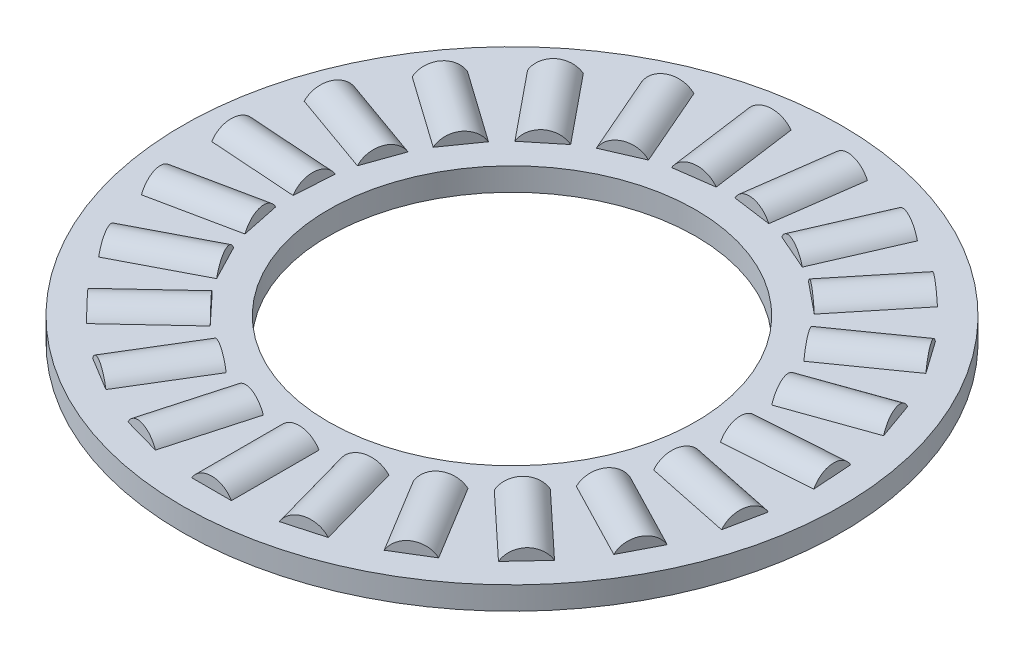
SolidWorks part; units mm, degrees
ref_plane "Front Plane" through (0, 0, 0) normal (0, 0, 1) x (1, 0, 0)
ref_plane "Top Plane" through (0, 0, 0) normal (0, 1, 0) x (1, 0, 0)
ref_plane "Right Plane" through (0, 0, 0) normal (1, 0, 0) x (0, 0, -1)
sketch "Sketch1" plane through (0, 0, 0) normal (1, 0, 0) x (0, 0, -1)
  line L0 (-14.2875, 0) -> (14.2875, 0) construction
  line L1 (0, -0.9922) -> (0, 0.9922) construction
  line L2 (-14.2875, 0.4961) -> (-7.9629, 0.4961)
  line L3 (-14.2875, 0.4961) -> (-14.2875, -0.4961)
  line L4 (-14.2875, -0.4961) -> (-7.9629, -0.4961)
  line L5 (-7.9629, 0.4961) -> (-7.9629, -0.4961)
  line L7 (-11.1252, 0.9922) -> (-11.1252, 0.4961) construction
  line L8 (-13.0226, 0.9922) -> (-9.2278, 0.9922) construction
  line L9 (-13.0226, 0.9922) -> (-13.0226, -0.9922) construction
  line L10 (-13.0226, -0.9922) -> (-9.2278, -0.9922) construction
  line L11 (-9.2278, 0.9922) -> (-9.2278, -0.9922) construction
  line L12 (14.2875, 0.9922) -> (14.2875, -0.9922) construction
  point P16 (-13.0226, 0)
  point P21 (14.2875, 0)
  dimension "OD" = 28.575
  dimension "ID" = 15.9258
  dimension "Washer Thickness" = 0.9922
  dimension "D1" = 3.7948
  dimension "Thickness" = 1.9844
sketch "Sketch6" plane through (0, 0, 0) normal (0, 1, 0) x (1, 0, 0)
  circle A0 centre (0, 0) radius 14.2875 construction
  circle A1 centre (0, 0) radius 7.9629 construction
  circle A2 centre (0, 0) radius 7.9375 construction
  dimension "For Shaft Diameter" = 15.875
  dimension "OD" = 28.575
  dimension "ID" = 15.9258
sketch "Sketch5" plane through (0, 0, 0) normal (1, 0, 0) x (0, 0, -1)
  line L1 (-14.2875, 0.4961) -> (-7.9629, 0.4961)
  line L2 (-14.2875, 0.4961) -> (-14.2875, -0.4961)
  line L3 (-14.2875, -0.4961) -> (-7.9629, -0.4961)
  line L4 (-7.9629, 0.4961) -> (-7.9629, -0.4961)
revolve "Revolve3" add sketch "Sketch5" angle 360 about L1
sketch "Sketch3" plane through (0, 0, 0) normal (1, 0, 0) x (0, 0, -1)
  line L0 (-13.0226, 0.9922) -> (-13.0226, -0.9922) construction
  line L1 (-13.0226, 0) -> (-9.2278, 0)
  line L2 (-13.0226, 0) -> (-13.0226, 0.9922)
  line L3 (-13.0226, 0.9922) -> (-9.2278, 0.9922)
  line L4 (-9.2278, 0) -> (-9.2278, 0.9922)
revolve "Cut-Revolve1" cut sketch "Sketch3" angle 360 about L1
sketch "Sketch2" plane through (0, 0, 0) normal (1, 0, 0) x (0, 0, -1)
  line L1 (-13.0226, 0) -> (-9.2278, 0)
  line L2 (-13.0226, 0) -> (-13.0226, 0.9922)
  line L3 (-13.0226, 0.9922) -> (-9.2278, 0.9922)
  line L4 (-9.2278, 0) -> (-9.2278, 0.9922)
revolve "Revolve2" add sketch "Sketch2" angle 360 about L1
ref_axis "Axis1" through (0, 0.9922, 0) along (0, -1, 0)
pattern_circular "CirPattern1" count 23 every 15.652 about axis through (0, 0.9922, 0) along (0, -1, 0) of bodies 187 411
pattern_circular "CirPattern2" count 23 every 15.652 about axis through (0, 0.9922, 0) along (0, -1, 0) of "Cut-Revolve1"
equation "\"Rollers@CirPattern1\"= \"OD@Sketch1\" * 20"
equation "\"Angle@CirPattern1\" = 360/\"Rollers@CirPattern1\""
equation "\"D1@CirPattern2\" = \"Rollers@CirPattern1\""
equation "\"D2@CirPattern2\" = \"Angle@CirPattern1\""
equation "\"D1@Sketch1\"=((\"OD@Sketch1\"-\"ID@Sketch1\")/2)*.6"
